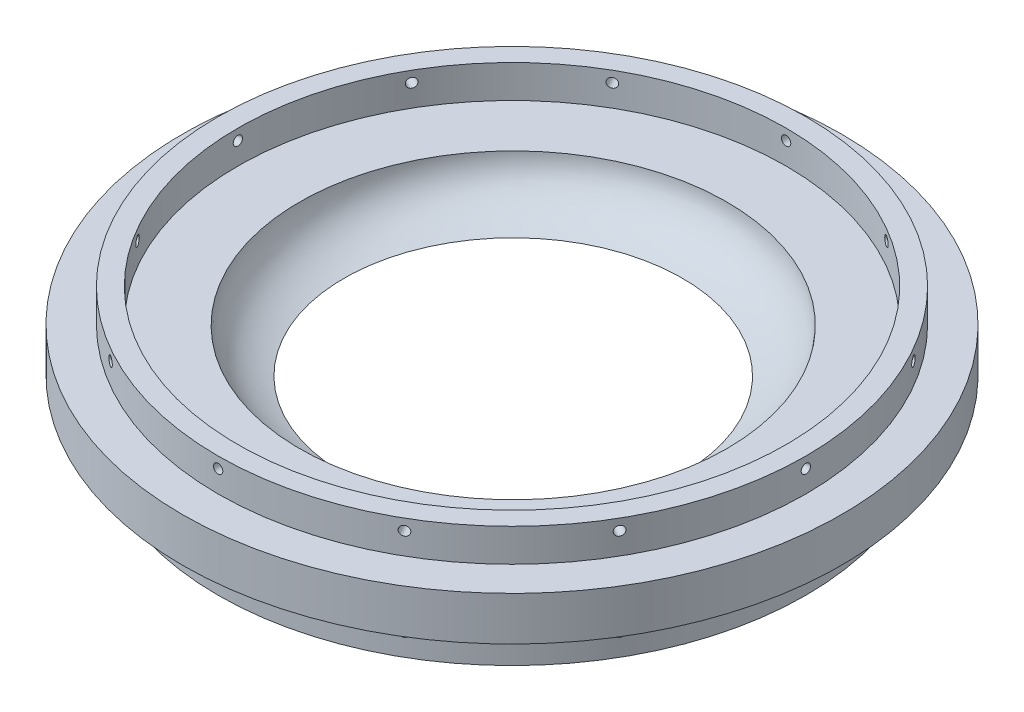
SolidWorks part; units mm, degrees
material "6061-T6 (SS)"
ref_plane "Front Plane" through (0, 0, 0) normal (0, 0, 1) x (1, 0, 0)
ref_plane "Top Plane" through (0, 0, 0) normal (0, 1, 0) x (1, 0, 0)
ref_plane "Right Plane" through (0, 0, 0) normal (1, 0, 0) x (0, 0, -1)
sketch "Sketch1" plane through (0, 0, 0) normal (0, 1, 0) x (1, 0, 0)
  line L5 (0, 0) -> (127.635, 0)
  line L6 (0, 0) -> (0, 127.635)
  line L7 (0, 127.635) -> (127.635, 127.635)
  line L8 (127.635, 0) -> (127.635, 127.635)
  dimension "D1" = 127.635
  dimension "D2" = 127.635
extrude "Boss-Extrude1" add sketch "Sketch1" along normal blind 12.7 contours L5 L8 L7 L6
sketch "Sketch12" plane through (0, 0, 0) normal (0, -1, 0) x (1, 0, 0)
  line L0 (63.8175, 0) -> (63.8175, -127.635) construction
  line L1 (0, 0) -> (127.635, 0) construction
  line L2 (0, -127.635) -> (127.635, -127.635) construction
  line L3 (0, -63.8175) -> (127.635, -63.8175) construction
  line L4 (0, 0) -> (0, -127.635) construction
  line L5 (127.635, 0) -> (127.635, -127.635) construction
  circle A0 centre (63.8175, -63.8175) radius 95.4151
  dimension "D1" = 190.8302
extrude "Boss-Extrude2" add sketch "Sketch12" against normal up to surface (12.7 mm away) contours A0 up to face at (63.8175, 12.7, -63.8175)
sketch "Sketch5" plane through (0, 12.7, 0) normal (0, 1, 0) x (1, 0, 0)
  circle A0 centre (63.8175, 63.8175) radius 46.355
  circle A3 centre (63.8175, 63.8175) radius 95.4151 construction
  dimension "D1" = 92.71
extrude "Cut-Extrude1" cut sketch "Sketch5" against normal blind 9.525
sketch "Sketch14" plane through (0, 12.7, 0) normal (0, -1, 0) x (1, 0, 0)
  line L0 (63.8175, -63.8175) -> (147.6375, -63.8175) construction
  line L1 (0, -19.2087) -> (0, 19.2087) construction
  line L2 (147.6375, -63.8175) -> (152.7175, -63.8175)
  line L3 (136.3808, -105.7742) -> (140.8401, -108.2104)
  circle A0 centre (63.8175, -63.8175) radius 46.355 construction
  arc A2 (147.6375, -63.8175) -> (136.3808, -105.7742) centre (63.8175, -63.8175) cw
  arc A3 (152.7175, -63.8175) -> (140.8401, -108.2104) centre (63.8175, -63.8175) cw
  point P0 (63.8175, -63.8175)
  dimension "D1" = 83.82
  dimension "D2" = 88.9
  dimension "D3" = 46.482
  dimension "D4" = 43.942
ref_plane "Support mirror reference plane" through (0, 4.7625, 0) normal (0, 1, 0) x (1, 0, 0)
sketch "Sketch25" plane through (0, 12.7, 0) normal (0, -1, 0) x (1, 0, 0)
  line L0 (63.8175, -63.8175) -> (123.0872, -4.5478) construction
  line L2 (123.0872, -4.5478) -> (126.6793, -0.9557)
  line L3 (144.7953, -42.1754) -> (149.6712, -40.7448)
  line L5 (63.8175, -63.8175) -> (147.6375, -63.8175) construction
  arc A2 (123.0872, -4.5478) -> (144.7953, -42.1754) centre (63.8175, -63.8175) cw
  arc A3 (126.6793, -0.9557) -> (149.6712, -40.7448) centre (63.8175, -63.8175) cw
  point P0 (63.8175, -63.8175)
  dimension "D1" = 83.82
  dimension "D2" = 88.9
  dimension "D3" = 46.482
  dimension "D4" = 43.942
  dimension "D5" = 45
sketch "Sketch30" plane through (0, 0, 0) normal (0, -1, 0) x (1, 0, 0)
  circle A0 centre (63.8175, -63.8175) radius 85.09
  circle A1 centre (63.8175, -63.8175) radius 79.375
  dimension "D1" = 170.18
  dimension "D2" = 158.75
extrude "Boss-Extrude3" add sketch "Sketch30" along normal blind 12.7
mirror "Mirror1" about plane through (0, 4.7625, 0) normal (0, 1, 0) of "Boss-Extrude3"
sketch "Sketch31" plane through (0, 0, 0) normal (0, -1, 0) x (-1, 0, 0)
  line L0 (-63.8175, -52.481) -> (-63.8175, 177.7216) construction
ref_plane "Plane1" through (0, 0, -148.9075) normal (0, 0, -1) x (-1, 0, 0)
ref_plane "Plane2" through (63.8175, 0, 0) normal (-1, 0, 0) x (0, 0, -1)
sketch "Sketch32" plane through (0, 0, -148.9075) normal (0, 0, -1) x (-1, 0, 0)
  line L4 (-63.8175, -87.3125) -> (-63.8175, 87.3125) construction
  line L5 (-148.9075, 0) -> (21.2725, 0) construction
  line L6 (21.2725, 12.7) -> (-148.9075, 12.7) construction
  circle A0 centre (-63.8175, -6.35) radius 1.3526
  circle A1 centre (-63.8175, 19.05) radius 1.3525
  dimension "D1" = 2.7051
  dimension "D2" = 2.7051
  dimension "D3" = 6.35
  dimension "D4" = 6.35
extrude "Cut-Extrude4" cut sketch "Sketch32" against normal blind 15.24
pattern_circular "CirPattern2" count 12 over 360 about axis through (63.8175, -12.7, -63.8175) along (0, 1, 0) of "Cut-Extrude4"
ref_plane "Plane3" through (0, 0, -63.754) normal (0, 0, 1) x (1, 0, 0)
sketch "Sketch35" plane through (0, 0, -63.754) normal (0, 0, 1) x (1, 0, 0)
  line L1 (126.0963, 12.7) -> (117.8413, 12.7)
  line L3 (110.1725, 12.7) -> (17.4625, 12.7) construction
  line L4 (17.4625, 0) -> (110.1725, 0) construction
  line L5 (17.4625, 0) -> (110.1725, 0)
  line L6 (64.2379, -16.1799) -> (64.2379, 15.7632) construction
  line L8 (102.2866, -2.54) -> (64.2379, -2.54)
  line L9 (64.2379, -2.54) -> (64.2379, 12.7)
  line L10 (64.2379, 12.7) -> (117.8413, 12.7)
  spline S0 degree 3 poles (126.0963, 12.7) (125.4021, 1.4511) (110.7266, -0.9032) (102.2866, -2.54) knots 0 0 0 0 1 1 1 1
  point P1 (0, 0)
  point P12 (112.7666, 0.5896)
  point P14 (107.0509, -4.7365)
  point P16 (0, 0)
  point P17 (0, 0)
  point P18 (102.2866, -4.6571)
  point P19 (112.3631, 2.236)
  point P20 (119.5354, 12.7)
  point P21 (0, 0)
  point P22 (117.5198, 7.2895)
  point P23 (0, 0)
  point P24 (0, 0)
  point P25 (0, 0)
  point P26 (113.2365, 0)
  dimension "D1" = 15.24
  dimension "D2" = 8.255
revolve "Cut-Revolve1" cut sketch "Sketch35" angle 360 about L6 region at (92.5272, 5.5387, -63.754)
